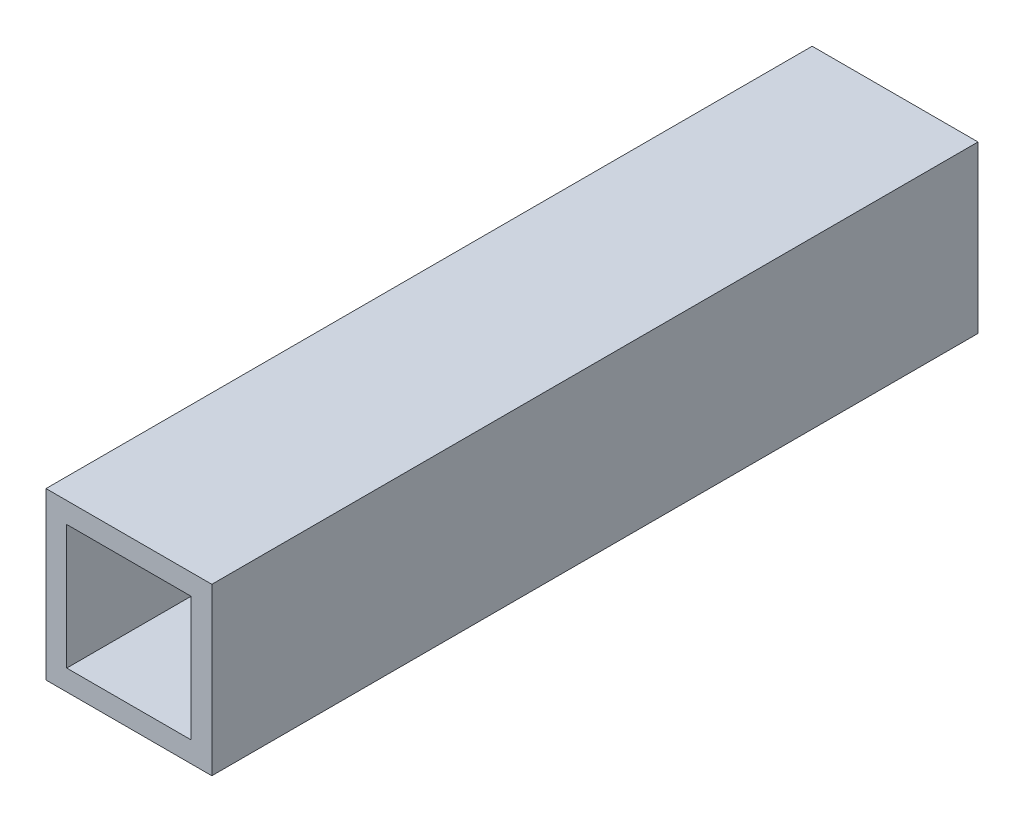
SolidWorks part; units mm, degrees
material "6061 Alloy"
ref_plane "Front Plane" through (0, 0, 0) normal (0, 0, 1) x (1, 0, 0)
ref_plane "Top Plane" through (0, 0, 0) normal (0, 1, 0) x (1, 0, 0)
ref_plane "Right Plane" through (0, 0, 0) normal (1, 0, 0) x (0, 0, -1)
sketch "Sketch1" plane through (0, 0, 0) normal (0, 0, 1) x (1, 0, 0)
  line L0 (12.7, 0) -> (9.525, 0) construction
  line L1 (-12.7, 0) -> (12.7, 0) construction
  line L2 (0, 12.7) -> (0, -12.7)
  point P7 (0, 0)
sketch "Sketch2" plane through (0, 0, 0) normal (1, 0, 0) x (0, 0, -1)
  line L0 (58.674, 0) -> (-58.674, 0)
  point P4 (0, 0)
  dimension "Length" = 117.348
sketch "Sketch3" plane through (0, 0, 0) normal (0, 0, 1) x (1, 0, 0)
  line L0 (-12.7, 0) -> (12.7, 0) construction
  line L5 (12.7, -12.7) -> (-12.7, -12.7)
  line L6 (12.7, -12.7) -> (12.7, 12.7)
  line L11 (12.7, 12.7) -> (-12.7, 12.7)
  line L12 (-12.7, -12.7) -> (-12.7, 12.7)
  line L14 (12.7, -12.7) -> (-12.7, 12.7) construction
  line L15 (12.7, 12.7) -> (-12.7, -12.7) construction
  line L16 (9.525, -9.525) -> (-9.525, -9.525)
  line L17 (9.525, -9.525) -> (9.525, 9.525)
  line L18 (9.525, 9.525) -> (-9.525, 9.525)
  line L19 (-9.525, -9.525) -> (-9.525, 9.525)
  line L20 (9.525, -9.525) -> (-9.525, 9.525) construction
  line L21 (9.525, 9.525) -> (-9.525, -9.525) construction
  point P0 (0, 0)
  point P5 (0, 0)
  point P13 (9.525, -12.7)
  dimension "D1" = 3.175
extrude "Boss-Extrude1" add sketch "Sketch3" along normal up to vertex (58.674 mm away) and the other way up to vertex (58.674 mm away) up to point (0, 0, 58.674) other way up to point (0, 0, -58.674)
sketch "Sketch5" plane through (0, 0, 0) normal (1, 0, 0) x (0, 0, -1)
  line L0 (-58.674, 0) -> (58.674, 0) construction
  line L3 (-58.674, -12.7) -> (-58.674, 12.7) construction
  line L4 (58.674, -12.7) -> (58.674, 12.7) construction
  point P6 (-30.099, 0)
  point P7 (-20.574, 0)
  point P8 (20.574, 0)
  point P10 (30.099, 0)
  dimension "D1" = 28.575
  dimension "D2" = 38.1
  dimension "D3" = 28.575
  dimension "D4" = 38.1
equation "\"D1@Sketch3\"=\"Wall thickness@Sketch1\""
equation "\"D1@Sketch5\"=\"Width@Sketch1\"*1.125"
equation "\"D2@Sketch5\"=\"Width@Sketch1\"*1.5"
equation "\"D3@Sketch5\"=\"D1@Sketch5\""
equation "\"D4@Sketch5\"=\"D2@Sketch5\""
equation "\"D2@Sketch3\"=\"Wall Thickness@Sketch1\""
